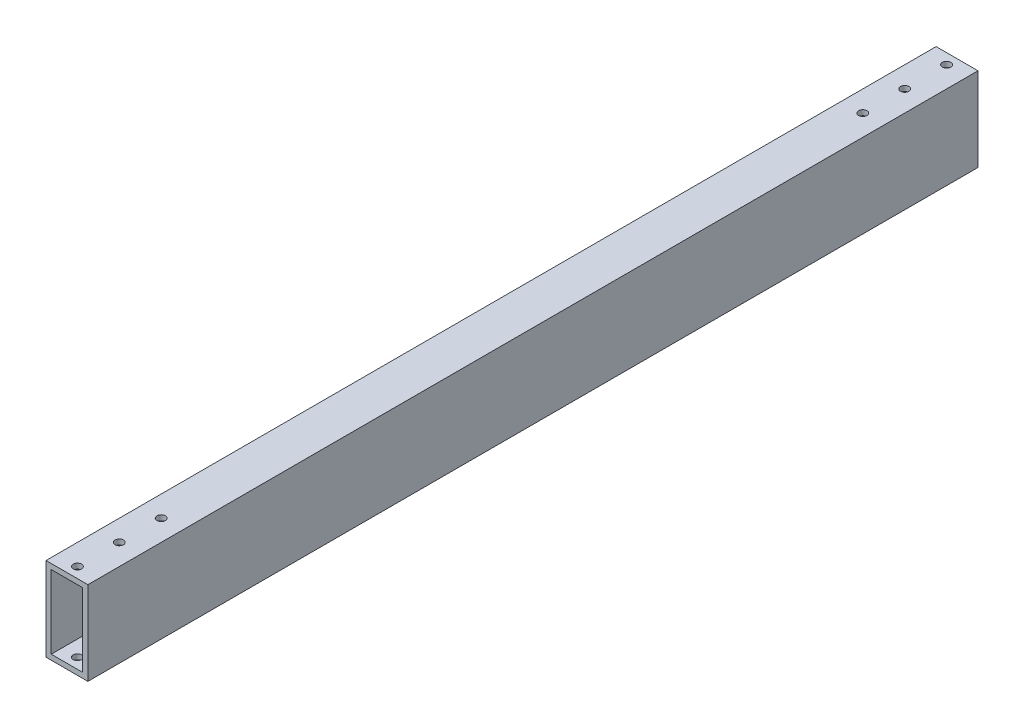
SolidWorks part; units mm, degrees
ref_plane "Front" through (0, 0, 0) normal (0, 0, 1) x (1, 0, 0)
ref_plane "Top" through (0, 0, 0) normal (0, 1, 0) x (1, 0, 0)
ref_plane "Right" through (0, 0, 0) normal (1, 0, 0) x (0, 0, -1)
sketch "Sketch1" plane through (0, 0, 0) normal (0, 0, 1) x (1, 0, 0)
  line L1 (-12.7, -25.4) -> (12.7, -25.4)
  line L2 (-12.7, -25.4) -> (-12.7, 25.4)
  line L3 (-12.7, 25.4) -> (12.7, 25.4)
  line L4 (12.7, -25.4) -> (12.7, 25.4)
  line L5 (-12.7, -25.4) -> (12.7, 25.4) construction
  line L6 (-12.7, 25.4) -> (12.7, -25.4) construction
  point P0 (0, 0)
  dimension "D1" = 25.4
  dimension "D2" = 50.8
extrude "Extrude-Thin1" add sketch "Sketch1" along normal blind 539.75 thin thin type one direction reverse wall 3.175
hole_wizard "#10 Clearance Hole1" positions "Sketch2" profile "Sketch3" hole size "#10" standard "ANSI Inch" end condition through all
sketch "Sketch2" plane through (0, 25.4, 0) normal (0, 1, 0) x (1, 0, 0)
  line L0 (12.7, -539.75) -> (-12.7, -539.75) construction
  line L1 (-12.7, -539.75) -> (-12.7, 0) construction
  point P0 (0, -533.4)
  point P2 (0, -508)
  point P4 (0, -482.6)
  point P6 (0, -6.35)
  point P8 (0, -31.75)
  point P10 (0, -57.15)
  dimension "D1" = 6.35
  dimension "D2" = 12.7
  dimension "D3" = 25.4
  dimension "D4" = 25.4
  dimension "D5" = 6.35
  dimension "D6" = 25.4
  dimension "D7" = 25.4
sketch "Sketch3" plane through (0, 25.4, 533.4) normal (1, 0, 0) x (0, 0, 1)
  line L0 (0, 0) -> (0, 50.8)
  line L1 (0, 50.8) -> (2.5527, 50.8)
  line L2 (2.5527, 50.8) -> (2.5527, 0)
  line L5 (2.5527, 0) -> (0, 0)
  line L11 (0, -6.35) -> (0, 107.95) construction
  dimension "Thru Hole Dia." = 5.1054
  dimension "Thru Hole Depth" = 50.8
